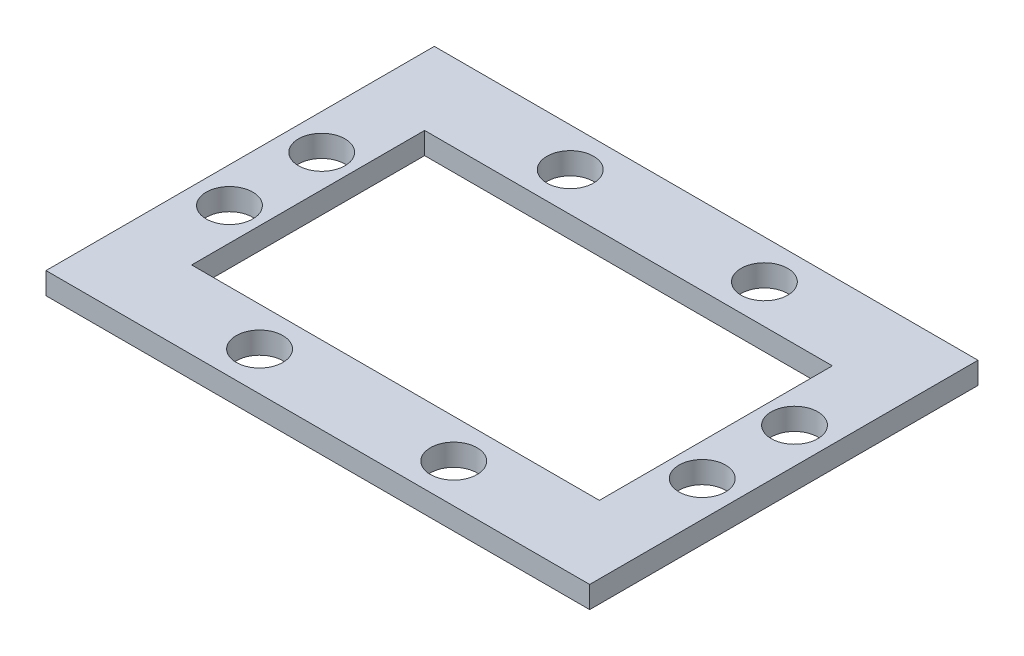
SolidWorks part; units mm, degrees
ref_plane "Front Plane" through (0, 0, 0) normal (0, 0, 1) x (1, 0, 0)
ref_plane "Top Plane" through (0, 0, 0) normal (0, 1, 0) x (1, 0, 0)
ref_plane "Right Plane" through (0, 0, 0) normal (1, 0, 0) x (0, 0, -1)
sketch "Sketch1" plane through (0, 0, 0) normal (0, 1, 0) x (1, 0, 0)
  line L0 (-24.35, 0) -> (24.35, 0) construction
  line L6 (-28, 20) -> (28, 20)
  line L7 (-21, 12) -> (21, 12)
  line L8 (-21, 12) -> (-21, -12)
  line L9 (-21, -12) -> (21, -12)
  line L10 (21, 12) -> (21, -12)
  line L11 (-21, 12) -> (21, -12) construction
  line L12 (-21, -12) -> (21, 12) construction
  line L13 (-24.35, 9.5) -> (24.35, 9.5)
  line L14 (-24.35, 9.5) -> (-24.35, -9.5)
  line L15 (-24.35, -9.5) -> (24.35, -9.5)
  line L16 (24.35, 9.5) -> (24.35, -9.5)
  line L17 (-24.35, 9.5) -> (24.35, -9.5) construction
  line L18 (-24.35, -9.5) -> (24.35, 9.5) construction
  line L19 (0, 0) -> (0, 9.5) construction
  line L20 (0, 0) -> (0, -9.5) construction
  line L21 (-24.35, -4.75) -> (24.35, -4.75) construction
  line L22 (-28, 20) -> (-28, -20)
  line L23 (-28, -20) -> (28, -20)
  line L24 (24.35, 4.75) -> (-24.35, 4.75) construction
  line L25 (28, 20) -> (28, -20)
  line L26 (-28, 20) -> (28, -20) construction
  line L27 (-28, -20) -> (28, 20) construction
  line L28 (-10, 16) -> (10, 16)
  line L29 (-10, 16) -> (-10, -16)
  line L30 (-10, -16) -> (10, -16)
  line L31 (10, 16) -> (10, -16)
  line L32 (-10, 16) -> (10, -16) construction
  line L33 (-10, -16) -> (10, 16) construction
  circle A0 centre (24.35, -4.75) radius 2.4
  circle A1 centre (24.35, 4.75) radius 2.4
  circle A2 centre (-24.35, -4.75) radius 2.4
  circle A3 centre (-24.35, 4.75) radius 2.4
  circle A5 centre (10, 16) radius 2.4
  circle A6 centre (10, -16) radius 2.4
  circle A7 centre (-10, -16) radius 2.4
  circle A8 centre (-10, 16) radius 2.4
  point P0 (0, 0)
  point P1 (0, 0)
  point P6 (0, 0)
  point P8 (0, 0)
  point P24 (0, -4.75)
  point P31 (0, 0)
  point P38 (0, 4.75)
  point P49 (-44.617, 29.413)
  point P50 (0, 0)
  point P51 (0, 0)
  dimension "D3" = 4.8
  dimension "D4" = 4.8
  dimension "D5" = 4.8
  dimension "D6" = 4.8
  dimension "D13" = 4.8
  dimension "D14" = 4.8
  dimension "D15" = 4.8
  dimension "D16" = 4.8
  dimension "D1" = 48.7
  dimension "D2" = 19
  dimension "D7" = 42
  dimension "D8" = 24
  dimension "D9" = 40
  dimension "D10" = 56
  dimension "D11" = 32
  dimension "D12" = 20
extrude "Boss-Extrude1" add sketch "Sketch1" along normal blind 2.25 contours L25 L6 L22 L23 A8 L28 A5 L31 L7 L10 L13 L16 A1 A0 L15 L9 A6 L30 A7 L29 L8 L14 A2 A3 | A3 L14 A2 L15 L8 L13 | A7 L30 A6 L31 L9 L29 | A8 L29 L7 L31 A5 L28 | A1 L16 L13 L10 L15 A0 region at (0, 0, -19.3118) region at (0, 0, -13.8749) region at (-22.4143, 0, 0) region at (22.4143, 0, 0) region at (0, 0, 13.8749)
